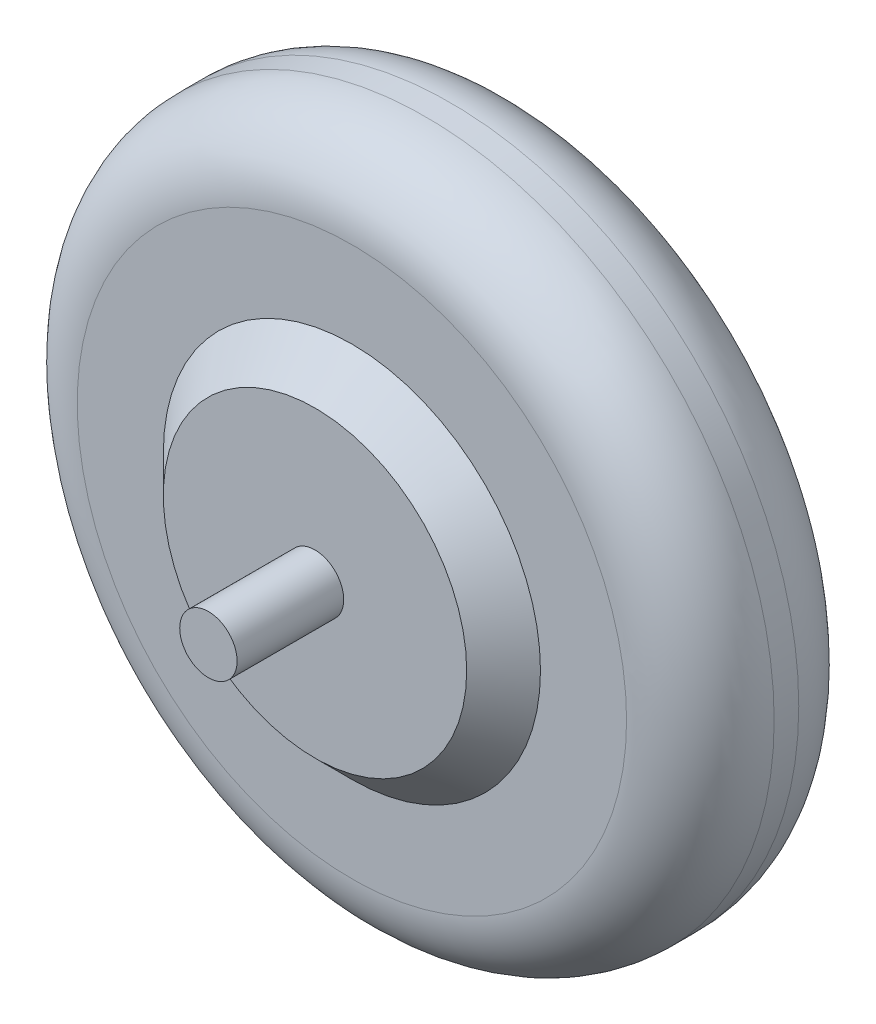
SolidWorks part; units mm, degrees
ref_plane "前视基准面" through (0, 0, 0) normal (0, 0, 1) x (1, 0, 0)
ref_plane "上视基准面" through (0, 0, 0) normal (0, 1, 0) x (1, 0, 0)
ref_plane "右视基准面" through (0, 0, 0) normal (1, 0, 0) x (0, 0, -1)
sketch "草图1" plane through (0, 0, 0) normal (0, 0, 1) x (1, 0, 0)
  circle A0 centre (0, 0) radius 85
  dimension "D1" = 170
extrude "凸台-拉伸1" add sketch "草图1" along normal mid plane 42
sketch "草图2" plane through (0, 0, 0) normal (0, 0, 1) x (1, 0, 0)
  circle A0 centre (0, 0) radius 47
  dimension "D1" = 94
extrude "凸台-拉伸2" add sketch "草图2" along normal mid plane 60
chamfer "倒角1" distance 10 angle 45 2 edges at (47, 0, -30) (47, 0, 30)
sketch "草图3" plane through (0, 0, -30) normal (0, 0, -1) x (-1, 0, 0)
  circle A0 centre (0, 0) radius 7
  dimension "D1" = 14
extrude "凸台-拉伸3" add sketch "草图3" along normal blind 32
cosmetic thread "装饰螺纹线1" parameters "D1"=28, "D2"=11.835
sketch "草图5" plane through (0, 0, -62) normal (0, 0, -1) x (-1, 0, 0)
  line L1 (5, -7) -> (-5, -7)
  line L2 (5, -7) -> (5, 7)
  line L3 (5, 7) -> (-5, 7)
  line L4 (-5, -7) -> (-5, 7)
  line L5 (5, -7) -> (-5, 7) construction
  line L6 (5, 7) -> (-5, -7) construction
  circle A0 centre (0, 0) radius 7 construction
  point P0 (0, 0)
  dimension "D1" = 10
extrude "切除-拉伸1" cut sketch "草图5" against normal blind 28 flip side to cut
chamfer "倒角3" distance 1 angle 45 2 edges at (0, -7, -62) (0, 7, -62)
sketch "草图7" plane through (0, 0, -62) normal (0, 0, -1) x (-1, 0, 0)
  circle A0 centre (0, 0) radius 3.5
  dimension "D1" = 7
extrude "切除-拉伸2" cut sketch "草图7" against normal blind 45
sketch "草图8" plane through (5, 0, 0) normal (1, 0, 0) x (0, 0, -1)
  line L0 (62, 3.3166) -> (62, -3.3166) construction
  circle A0 centre (62, 0) radius 7
  dimension "D1" = 14
extrude "切除-拉伸4" cut sketch "草图8" against normal blind 5 contours A0
fillet "圆角1" radius 18 2 edges at (85, 0, -21) (85, 0, 21)
sketch "草图10" plane through (0, 0, 30) normal (0, 0, 1) x (1, 0, 0)
  circle A0 centre (0, 0) radius 7
  circle A1 centre (0, 0) radius 7 construction
extrude "凸台-拉伸4" add sketch "草图10" along normal blind 26
cosmetic thread "装饰螺纹线2" parameters "D1"=22, "D2"=11.835
